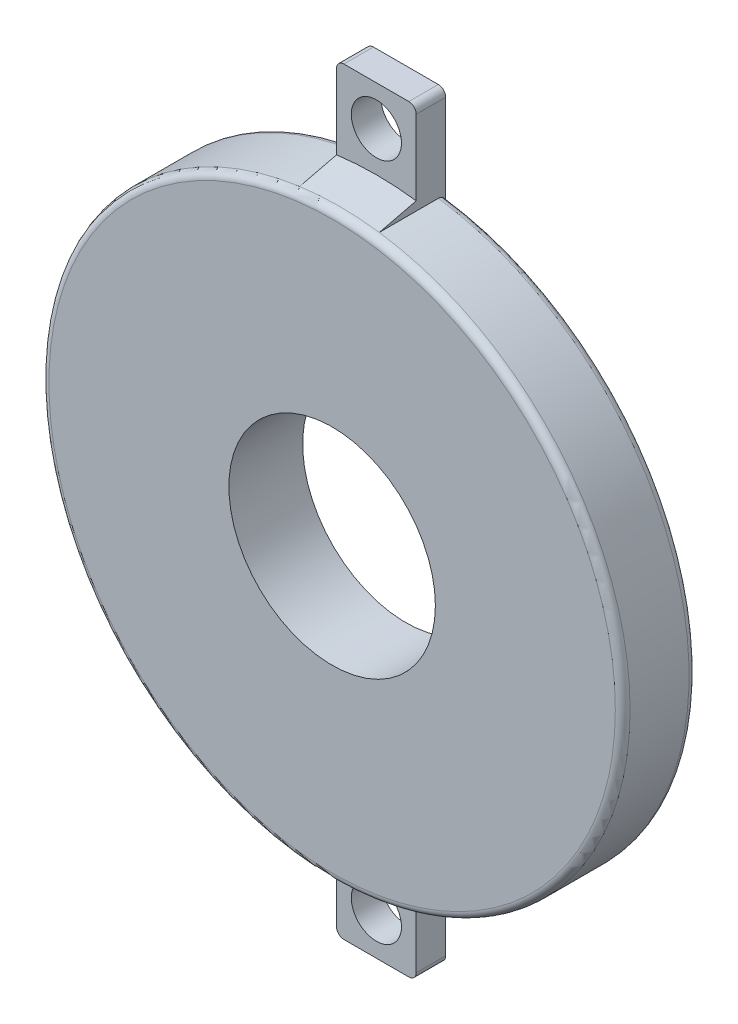
SolidWorks part; units mm, degrees
ref_plane "Alzado" through (0, 0, 0) normal (1, 0, 0) x (0, 1, 0)
ref_plane "Planta" through (0, 0, 0) normal (0, 0, 1) x (0, 1, 0)
ref_plane "Vista lateral" through (0, 0, 0) normal (0, 1, 0) x (-1, 0, 0)
sketch "Croquis2" plane through (0, 0, 0) normal (0, 0, 1) x (0, 1, 0)
  line L0 (19.5141, -2.7) -> (25.7, -2.7)
  line L1 (25.7, -2.7) -> (25.7, 2.7)
  line L2 (25.7, 2.7) -> (19.5141, 2.7)
  line L3 (19.7, 0) -> (12.9846, 0) construction
  line L4 (0, 0) -> (0, 2.6834) construction
  line L5 (-19.5141, -2.7) -> (-25.7, -2.7)
  line L6 (-25.7, -2.7) -> (-25.7, 2.7)
  line L7 (-25.7, 2.7) -> (-19.5141, 2.7)
  circle A0 centre (0, 0) radius 19.7
  circle A1 centre (23, 0) radius 1.7
  circle A2 centre (-23, 0) radius 1.7
  circle A3 centre (0, 0) radius 7
  dimension "D3" = 39.4
  dimension "D5" = 3.4
  dimension "D6" = 14
  dimension "D1" = 5.4
  dimension "D2" = 6
  dimension "D4" = 3.3
extrude "Saliente-Extruir1" add sketch "Croquis2" along normal blind 5 contours A0 region at (19.1428, 0, 0)
extrude "Saliente-Extruir2" add sketch "Croquis2<3>" along normal blind 2 contours A0 L7 L6 L5 A2 | A0 L0 L1 L2 A1 region at (1.3588, 19.7354, 0) region at (2.6179, -22.607, 0)
sketch "Croquis2<3>" plane through (0, 0, 0) normal (0, 0, 1) x (0, 1, 0) same geometry as "Croquis2"
fillet "Redondeo1" radius 0.5 4 edges at (2.7, -25.7, 1) (-2.7, -25.7, 1) (2.7, 25.7, 1) (-2.7, 25.7, 1)
fillet "Redondeo4" radius 0.5 3 edges at (19.7, 0, 0) (-19.7, 0, 0) (19.7, 0, 5)
chamfer "Chaflán2" distance 0.6 distance2 2.5 2 edges at (0, 19.7, 2) (0, -19.7, 2) first distance on face at (1.7, 23, 2) first distance on face at (0, -23.5369, 2)
